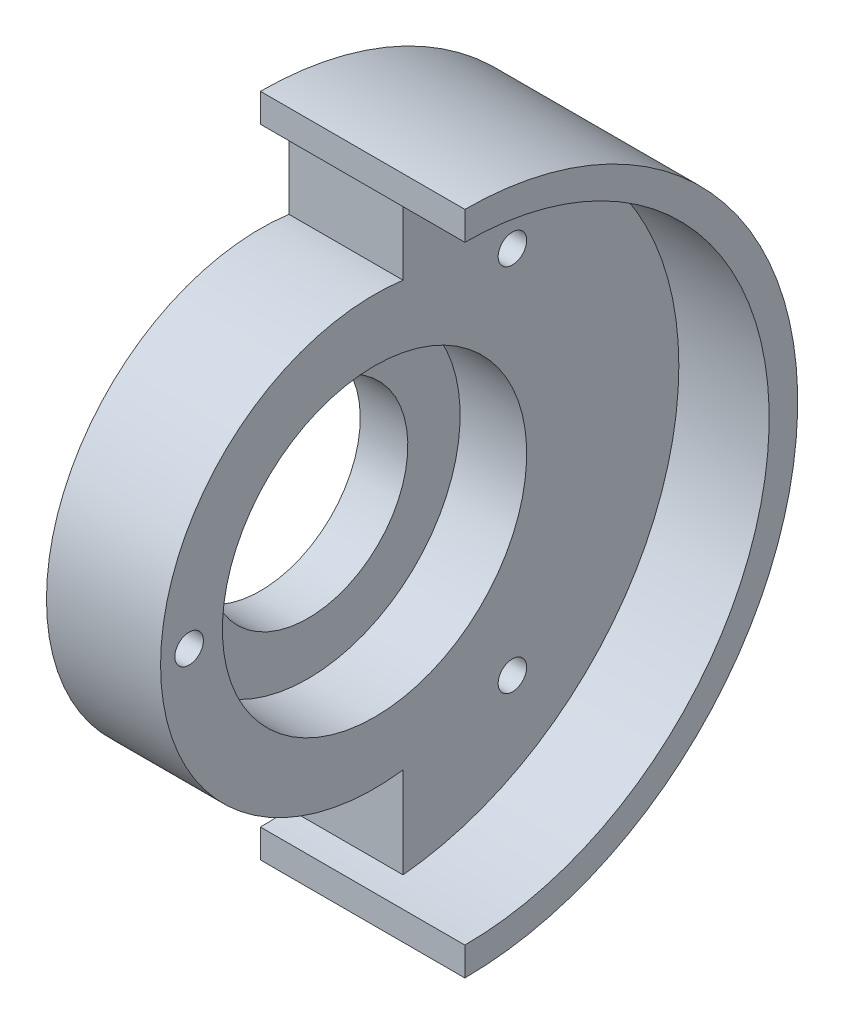
SolidWorks part; units mm, degrees
ref_plane "Front Plane" through (0, 0, 0) normal (0, 0, 1) x (1, 0, 0)
ref_plane "Top Plane" through (0, 0, 0) normal (0, 1, 0) x (1, 0, 0)
ref_plane "Right Plane" through (0, 0, 0) normal (1, 0, 0) x (0, 0, -1)
sketch "Sketch1" plane through (0, 0, 0) normal (0, 0, 1) x (1, 0, 0)
  line L0 (21.5, 35) -> (21.5, 32)
  line L1 (21.5, 32) -> (12, 32)
  line L2 (12, 32) -> (12, 16)
  line L3 (12, 16) -> (5, 16)
  line L4 (5, 16) -> (5, 10.5)
  line L5 (5, 10.5) -> (0, 10.5)
  line L6 (0, 10.5) -> (0, 35)
  line L7 (0, 35) -> (21.5, 35)
  line L8 (21.5, 0) -> (0, 0) construction
  point P10 (40.0475, 0)
  point P11 (0, 0)
  point P14 (0, 0)
  dimension "D1" = 5
  dimension "D2" = 7
  dimension "D3" = 9.5
  dimension "D4" = 10.5
  dimension "D5" = 16
  dimension "D6" = 32
  dimension "D7" = 35
revolve "Revolve1" add sketch "Sketch1" angle 360 about L8
sketch "Sketch2" plane through (12, 0, 0) normal (1, 0, 0) x (0, 0, -1)
  line L0 (3, 22.2991) -> (3, 31.8591)
  line L1 (3, -22.2991) -> (3, -31.8591)
  line L2 (0, 35) -> (0, 32)
  line L3 (0, -32) -> (0, -35)
  arc A0 (3, 31.8591) -> (0, 32) centre (0, 0) ccw
  arc A1 (3, 22.2991) -> (3, -22.2991) centre (0, 0) ccw
  circle A2 centre (-19.5, 0) radius 1.5
  circle A3 centre (0, 0) radius 32 construction
  arc A4 (3, 22.2991) -> (3, -22.2991) centre (0, 0) ccw construction
  circle A5 centre (14.5, -19.4374) radius 1.5
  circle A6 centre (14.5, 19.4374) radius 1.5
  circle A7 centre (14.5, 19.4374) radius 1.5 construction
  circle A8 centre (-19.5, 0) radius 1.5 construction
  circle A9 centre (14.5, -19.4374) radius 1.5 construction
  arc A10 (0, 35) -> (0, -35) centre (0, 0) ccw
  circle A11 centre (0, 0) radius 35 construction
  arc A12 (0, -32) -> (3, -31.8591) centre (0, 0) ccw
extrude "Cut-Extrude1" cut sketch "Sketch2" against normal through all both and the other way through all
sketch "Sketch3" plane through (0, 0, 0) normal (-1, 0, 0) x (0, 0, 1)
  circle A0 centre (-14.5, 19.4374) radius 2.75
  circle A1 centre (19.5, 0) radius 2.75
  circle A2 centre (-14.5, -19.4374) radius 2.75
  dimension "D1" = 5.5
extrude "Cut-Extrude2" cut sketch "Sketch3" against normal blind 5
